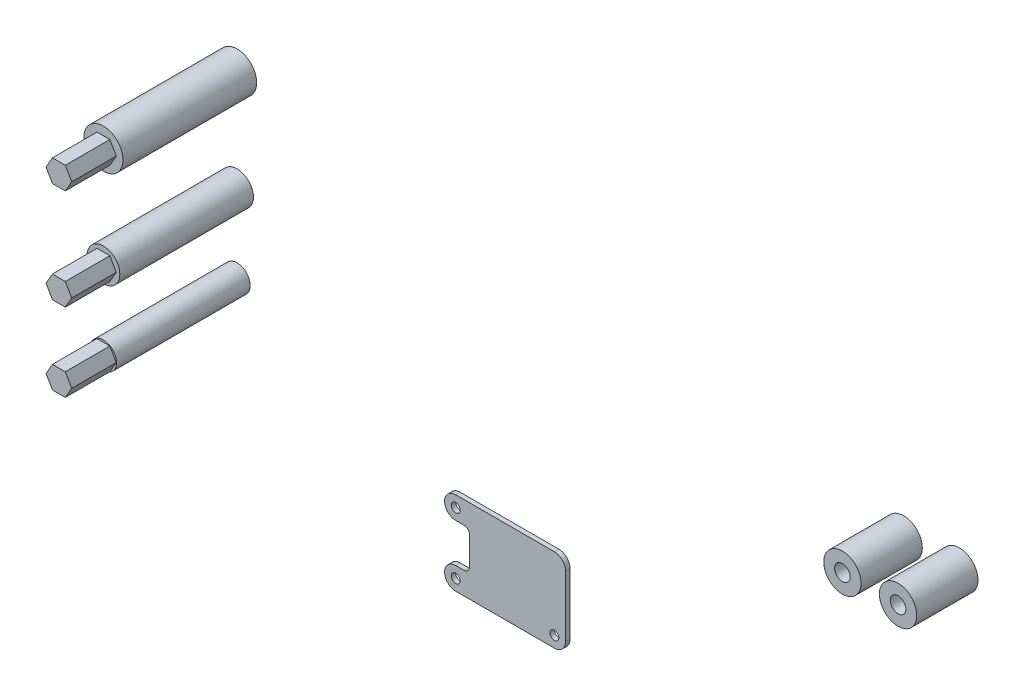
SolidWorks part; units mm, degrees
ref_plane "Front Plane" through (0, 0, 0) normal (0, 0, 1) x (1, 0, 0)
ref_plane "Top Plane" through (0, 0, 0) normal (0, 1, 0) x (1, 0, 0)
ref_plane "Right Plane" through (0, 0, 0) normal (1, 0, 0) x (0, 0, -1)
sketch "Sketch1" plane through (0, 0, 0) normal (0, 0, 1) x (1, 0, 0)
  line L0 (41.5252, 85.2495) -> (55.5016, 85.2495) construction
  line L1 (58.7537, 81.2495) -> (58.7537, 83.2495)
  line L2 (40.5252, 83.2495) -> (39.0252, 83.2495)
  line L3 (39.0252, 79.2495) -> (56.7537, 79.2495)
  line L4 (41.5252, 84.2495) -> (41.5252, 85.2495)
  line L5 (-0.0481, 105.8254) -> (0.9333, 107.5254)
  line L6 (0.9333, 107.5254) -> (-0.0481, 109.2254)
  line L7 (-0.0481, 109.2254) -> (-2.0111, 109.2254)
  line L8 (-2.0111, 109.2254) -> (-2.9926, 107.5254)
  line L9 (-2.9926, 107.5254) -> (-2.0111, 105.8254)
  line L10 (-2.0111, 105.8254) -> (-0.0481, 105.8254)
  line L11 (0.2405, 119.3642) -> (1.5107, 121.5642)
  line L12 (1.5107, 121.5642) -> (0.2405, 123.7642)
  line L13 (0.2405, 123.7642) -> (-2.2998, 123.7642)
  line L14 (-2.2998, 123.7642) -> (-3.57, 121.5642)
  line L15 (-3.57, 121.5642) -> (-2.2998, 119.3642)
  line L16 (-2.2998, 119.3642) -> (0.2405, 119.3642)
  line L17 (0.5292, 136.9341) -> (2.088, 139.6341)
  line L18 (2.088, 139.6341) -> (0.5292, 142.3341)
  line L19 (0.5292, 142.3341) -> (-2.5885, 142.3341)
  line L20 (-2.5885, 142.3341) -> (-4.1473, 139.6341)
  line L21 (-4.1473, 139.6341) -> (-2.5885, 136.9341)
  line L22 (-2.5885, 136.9341) -> (0.5292, 136.9341)
  line L23 (2.088, 139.6341) -> (2.488, 139.6341) construction
  line L24 (1.5107, 121.5642) -> (1.9107, 121.5642) construction
  line L25 (0.9333, 107.5254) -> (1.3333, 107.5254) construction
  line L26 (41.5252, 85.2495) -> (41.5252, 89.2495)
  line L27 (40.5252, 90.2495) -> (39.0252, 90.2495)
  line L28 (39.0252, 94.2495) -> (51.5016, 94.2495)
  line L29 (53.5016, 87.2495) -> (53.5016, 92.2495)
  line L30 (55.5016, 85.2495) -> (56.7537, 85.2495)
  line L31 (58.7537, 83.2495) -> (58.7537, 92.2495)
  line L32 (56.7537, 94.2495) -> (51.5016, 94.2495)
  circle A0 centre (39.0252, 81.2495) radius 2
  circle A1 centre (56.7537, 81.2495) radius 2
  circle A2 centre (39.0252, 81.2495) radius 0.8
  circle A3 centre (56.7537, 81.2495) radius 0.8
  arc A4 (58.7537, 92.2495) -> (56.7537, 94.2495) centre (56.7537, 92.2495) ccw
  arc A5 (40.5252, 83.2495) -> (41.5252, 84.2495) centre (40.5252, 84.2495) ccw
  circle A6 centre (-1.0296, 107.5254) radius 1.7 construction
  circle A7 centre (-1.0296, 121.5642) radius 2.2 construction
  circle A8 centre (-1.0296, 139.6341) radius 2.7 construction
  circle A9 centre (-1.0296, 107.5254) radius 2.363
  circle A10 centre (-1.0296, 121.5642) radius 2.9403
  circle A11 centre (-1.0296, 139.6341) radius 3.5177
  circle A12 centre (-1.0296, 139.6341) radius 1.5
  circle A13 centre (-1.0296, 121.5642) radius 1.25
  circle A14 centre (-1.0296, 107.5254) radius 1.05
  circle A15 centre (39.0252, 92.2495) radius 2
  circle A16 centre (39.0252, 92.2495) radius 0.8
  arc A17 (41.5252, 89.2495) -> (40.5252, 90.2495) centre (40.5252, 89.2495) ccw
  circle B0 centre (78.6519, 127.0575) radius 1.4
  circle B1 centre (78.6519, 127.0575) radius 3.35
  circle B2 centre (78.736, 101.9939) radius 0.85
  circle B3 centre (78.736, 101.9939) radius 2.9
  circle B4 centre (78.736, 114.8621) radius 1.1
  circle B5 centre (78.736, 114.8621) radius 2.7
  circle B6 centre (88.6519, 127.0575) radius 1.4
  circle B7 centre (88.6519, 127.0575) radius 3.35
  circle B8 centre (98.6519, 127.0575) radius 1.4
  circle B9 centre (98.6519, 127.0575) radius 3.35
  circle B10 centre (108.6519, 127.0575) radius 1.4
  circle B11 centre (108.6519, 127.0575) radius 3.35
  circle B12 centre (118.6519, 127.0575) radius 1.4
  circle B13 centre (118.6519, 127.0575) radius 3.35
  circle B14 centre (128.6519, 127.0575) radius 1.4
  circle B15 centre (128.6519, 127.0575) radius 3.35
  circle B16 centre (88.736, 101.9939) radius 0.85
  circle B17 centre (88.736, 101.9939) radius 2.9
  circle B18 centre (98.736, 101.9939) radius 0.85
  circle B19 centre (98.736, 101.9939) radius 2.9
  circle B20 centre (108.736, 101.9939) radius 0.85
  circle B21 centre (108.736, 101.9939) radius 2.9
  circle B22 centre (88.736, 114.8621) radius 1.1
  circle B23 centre (88.736, 114.8621) radius 2.7
  circle B24 centre (76.8787, 139.9756) radius 1.6
  circle B25 centre (76.8787, 139.9756) radius 4
  circle B26 centre (86.8787, 139.9756) radius 1.6
  circle B27 centre (86.8787, 139.9756) radius 4
  dimension "D1" = 4
  dimension "D2" = 1.6
  dimension "D4" = 2
  dimension "D6" = 1
  dimension "D11" = 3
  dimension "D12" = 2.5
  dimension "D13" = 2.1
  dimension "D18" = 4
  dimension "D19" = 1.6
  dimension "D20" = 1
  dimension "D26" = 2
  dimension "D3" = 4
  dimension "D5" = 2.5
  dimension "D7" = 17.7284
  dimension "D8" = 3.4
  dimension "D9" = 5.4
  dimension "D10" = 4.4
  dimension "D14" = 0.4
  dimension "D15" = 0.4
  dimension "D16" = 0.4
  dimension "D17" = 11
  dimension "D23" = 6
  dimension "D24" = 4
  dimension "D25" = 2
sketch_block_instance "M2.5 spacer-10"
sketch_block "M2.5 spacer" parameters "D1"=2.8, "D3"=6.7, "D4"=2.7, "D2"=4.7
sketch_block_instance "M1.6 spacer-11"
sketch_block "M1.6 spacer" parameters "D1"=1.7, "D3"=5.8, "D4"=1.8, "D2"=3.8
sketch_block_instance "M2 spacer-4"
sketch_block "M2 spacer" parameters "D1"=2.2, "D3"=1, "D4"=2.2, "D2"=3.8
sketch_block_instance "M2.5 spacer-15"
sketch_block_instance "M2.5 spacer-16"
sketch_block_instance "M2.5 spacer-17"
sketch_block_instance "M2.5 spacer-18"
sketch_block_instance "M2.5 spacer-19"
sketch_block_instance "M1.6 spacer-14"
sketch_block_instance "M1.6 spacer-15"
sketch_block_instance "M1.6 spacer-16"
sketch_block_instance "M2 spacer-6"
sketch_block_instance "M3 spacer-1"
sketch_block "M3 spacer" parameters "D1"=3.2, "D2"=8, "D3"=5.6
sketch_block_instance "M3 spacer-2"
extrude "Boss-Extrude1" add sketch "Sketch1" along normal blind 8 contours A11 L22 L21 L20 L19 L18 L17 | A10 L16 L15 L14 L13 L12 L11 | A9 L10 L9 L8 L7 L6 L5 region at (-3.3258, 107.5254, 0) region at (-3.8868, 121.5642, 0) region at (-4.4478, 139.6341, 0)
extrude "Boss-Extrude2" add sketch "Sketch1<3>" along normal blind 16 from surface contours L9 L10 L5 L6 L7 L8 A14 | A9 L10 L9 L8 L7 L6 L5 | A10 L16 L15 L14 L13 L12 L11 | L15 L16 L11 L12 L13 L14 A13 | A11 L22 L21 L20 L19 L18 L17 | L21 L22 L17 L18 L19 L20 A12 region at (-1.0296, 105.8773, 0) region at (-1.0296, 119.4314, 0) region at (-1.0296, 137.0166, 0) region at (-3.3258, 107.5254, 0) region at (-3.8868, 121.5642, 0) region at (-4.4478, 139.6341, 0) starting at face at (-1.0296, 139.6341, 8)
sketch "Sketch1<3>" plane through (0, 0, 0) normal (0, 0, 1) x (1, 0, 0) same geometry as "Sketch1"
sketch "Sketch2" plane through (0, 0, 24) normal (0, 0, 1) x (1, 0, 0)
  line B0 (0.1251, 137.6341) -> (1.2798, 139.6341)
  line B1 (1.2798, 139.6341) -> (0.1251, 141.6341)
  line B2 (0.1251, 141.6341) -> (-2.1843, 141.6341)
  line B3 (-2.1843, 141.6341) -> (-3.339, 139.6341)
  line B4 (-3.339, 139.6341) -> (-2.1843, 137.6341)
  line B5 (-2.1843, 137.6341) -> (0.1251, 137.6341)
  circle B6 centre (-1.0296, 139.6341) radius 2 construction
  line B7 (0.1251, 119.5642) -> (1.2798, 121.5642)
  line B8 (1.2798, 121.5642) -> (0.1251, 123.5642)
  line B9 (0.1251, 123.5642) -> (-2.1843, 123.5642)
  line B10 (-2.1843, 123.5642) -> (-3.339, 121.5642)
  line B11 (-3.339, 121.5642) -> (-2.1843, 119.5642)
  line B12 (-2.1843, 119.5642) -> (0.1251, 119.5642)
  circle B13 centre (-1.0296, 121.5642) radius 2 construction
  line B14 (0.1251, 105.5254) -> (1.2798, 107.5254)
  line B15 (1.2798, 107.5254) -> (0.1251, 109.5254)
  line B16 (0.1251, 109.5254) -> (-2.1843, 109.5254)
  line B17 (-2.1843, 109.5254) -> (-3.339, 107.5254)
  line B18 (-3.339, 107.5254) -> (-2.1843, 105.5254)
  line B19 (-2.1843, 105.5254) -> (0.1251, 105.5254)
  circle B20 centre (-1.0296, 107.5254) radius 2 construction
sketch_block_instance "T4-hex-1"
sketch_block "T4-hex" parameters "D1"=4
sketch_block_instance "T4-hex-2"
sketch_block_instance "T4-hex-3"
extrude "Boss-Extrude3" add sketch "Sketch2" along normal blind 8
chamfer "Chamfer1" distance 1 angle 60 1 edges at (0.0204, 107.5254, 24) first distance on face at (0.0204, 107.5254, 24)
chamfer "Chamfer2" distance 1.2 angle 60 1 edges at (0.2204, 121.5642, 24) first distance on face at (0.2204, 121.5642, 24)
chamfer "Chamfer3" distance 1.4 angle 60 1 edges at (0.4704, 139.6341, 24) first distance on face at (0.4704, 139.6341, 24)
extrude "Boss-Extrude4" add sketch "Sketch1<5>" along normal blind 0.8 separate body contours L30 L29 L28 A15 L27 A17 L26 L4 A5 L2 A0 L3 A1 L1 | A0 A2 | A1 A3 | A15 A16 region at (49.468, 87.0237, 0) region at (58.1279, 79.8753, 0) region at (37.0818, 81.2495, 0) region at (40.3994, 93.6237, 0)
sketch "Sketch1<5>" plane through (0, 0, 0) normal (0, 0, 1) x (1, 0, 0) same geometry as "Sketch1"
extrude "Boss-Extrude5" add sketch "Sketch1<7>" along normal blind 11 separate body contours B15 B14 | B13 B12 region at (115.3966, 127.0575, 0) region at (125.3966, 127.0575, 0)
sketch "Sketch1<7>" plane through (0, 0, 0) normal (0, 0, 1) x (1, 0, 0) same geometry as "Sketch1"
